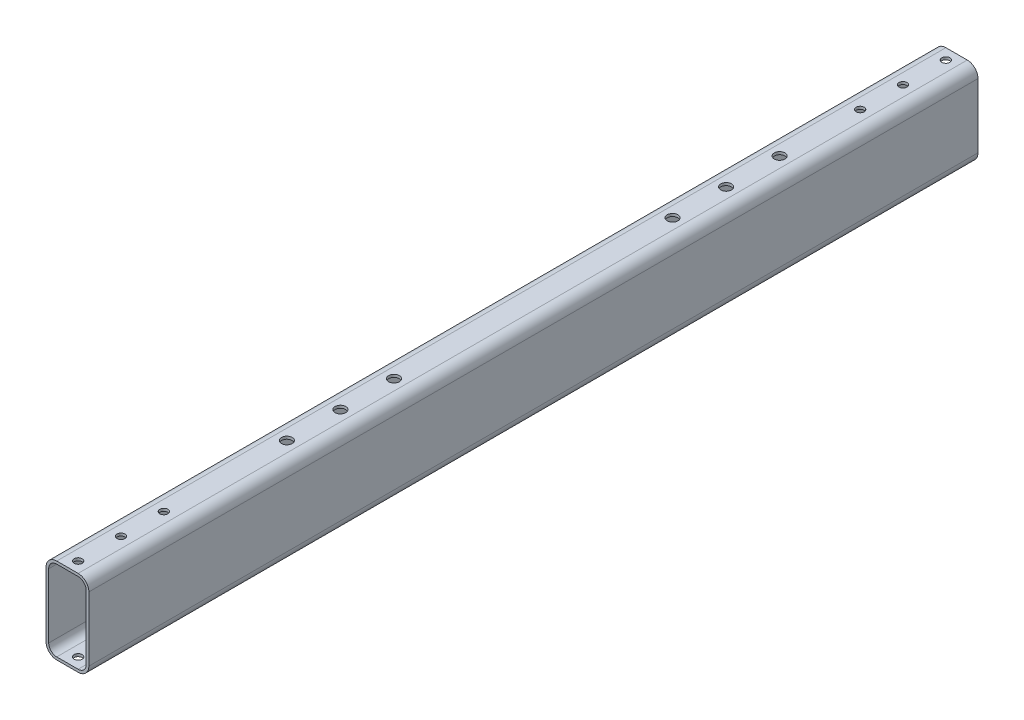
SolidWorks part; units mm, degrees
material "6061-T6 (SS)"
ref_plane "Front Plane" through (0, 0, 0) normal (0, 0, 1) x (1, 0, 0)
ref_plane "Top Plane" through (0, 0, 0) normal (0, 1, 0) x (1, 0, 0)
ref_plane "Right Plane" through (0, 0, 0) normal (1, 0, 0) x (0, 0, -1)
sketch "Sketch1" plane through (0, 0, 0) normal (0, 0, 1) x (1, 0, 0)
  line L1 (-6.35, -25.4) -> (6.35, -25.4)
  line L2 (-12.7, -19.05) -> (-12.7, 19.05)
  line L3 (-6.35, 25.4) -> (6.35, 25.4)
  line L4 (12.7, -19.05) -> (12.7, 19.05)
  line L5 (-12.7, -25.4) -> (12.7, 25.4) construction
  line L6 (-12.7, 25.4) -> (12.7, -25.4) construction
  arc A0 (-12.7, -19.05) -> (-6.35, -25.4) centre (-6.35, -19.05) ccw
  arc A1 (6.35, -25.4) -> (12.7, -19.05) centre (6.35, -19.05) ccw
  arc A2 (6.35, 25.4) -> (12.7, 19.05) centre (6.35, 19.05) cw
  arc A3 (-12.7, 19.05) -> (-6.35, 25.4) centre (-6.35, 19.05) cw
  point P0 (0, 0)
  dimension "D3" = 6.35
  dimension "D1" = 50.8
  dimension "D2" = 25.4
extrude "Extrude-Thin1" add sketch "Sketch1" along normal blind 527.05 thin thin type one direction reverse wall 1.5875
hole_wizard "3/16 (0.1875) Diameter Hole1" positions "3DSketch1" profile "Sketch3" hole size "3/16" standard "ANSI Inch" end condition through all
sketch3d "3DSketch1"
  line L1 (6.35, 25.4, 0) -> (-6.35, 25.4, 0) construction
  line L6 (0, 25.4, 527.05) -> (0, 25.4, 0) construction
  line L7 (6.35, 25.4, 527.05) -> (-6.35, 25.4, 527.05) construction
  point P57 (0, 25.4, 6.35)
  point P59 (0, 25.4, 31.75)
  point P61 (0, 25.4, 57.15)
  point P63 (0, 25.4, 495.3)
  point P65 (0, 25.4, 469.9)
  point P67 (0, 25.4, 520.7)
  dimension "D1" = 25.4
  dimension "D2" = 25.4
  dimension "D3" = 6.35
  dimension "D4" = 25.4
  dimension "D5" = 25.4
  dimension "D6" = 6.35
sketch "Sketch3" plane through (0, 25.4, 520.7) normal (1, 0, 0) x (0, 0, 1)
  line L0 (0, 0) -> (0, 50.8)
  line L1 (0, 50.8) -> (2.3812, 50.8)
  line L2 (2.3812, 50.8) -> (2.3812, 0)
  line L5 (2.3812, 0) -> (0, 0)
  line L11 (0, -6.35) -> (0, 107.95) construction
  dimension "Thru Hole Dia." = 4.7625
  dimension "Thru Hole Depth" = 50.8
hole_wizard "3/16 (0.195) Diameter Hole1" positions "Sketch4" profile "Sketch5" hole size "3/16" standard "ANSI Inch" end condition up to next
sketch "Sketch4" plane through (0, -25.4, 0) normal (0, -1, 0) x (-1, 0, 0)
  point P3 (3.175, -89.4447)
  point P6 (-3.175, -114.8447)
  point P9 (3.175, -140.2447)
  point P12 (-3.175, -165.6447)
  point P15 (-3.175, -318.0447)
  point P18 (3.175, -343.4447)
  point P21 (-3.175, -368.8447)
  point P24 (3.175, -394.2447)
sketch "Sketch5" plane through (-3.175, -25.4, 89.4447) normal (1, 0, 0) x (0, 0, -1)
  line L0 (0, 0) -> (0, 1.5875)
  line L1 (0, 1.5875) -> (2.4765, 1.5875)
  line L2 (2.4765, 1.5875) -> (2.4765, 0)
  line L5 (2.4765, 0) -> (0, 0)
  line L11 (0, -6.35) -> (0, 107.95) construction
  dimension "Thru Hole Dia." = 4.953
  dimension "Thru Hole Depth" = 1.5875
hole_wizard "1/4 (0.25) Diameter Hole1" positions "Sketch7" profile "Sketch6" hole size "1/4" standard "ANSI Inch"
sketch "Sketch7" plane through (0, 25.4, 0) normal (0, 1, 0) x (1, 0, 0)
  point P0 (0, -104.85)
  point P3 (0, -136.6)
  point P6 (0, -168.35)
  point P9 (0, -396.9748)
  point P12 (0, -365.2248)
  point P15 (0, -333.4748)
sketch "Sketch6" plane through (0, 25.4, 104.85) normal (1, 0, 0) x (0, 0, 1)
  line L0 (0, 0) -> (0, 27.3077)
  line L1 (0, 27.3077) -> (3.175, 25.4)
  line L2 (3.175, 25.4) -> (3.175, 0)
  line L5 (3.175, 0) -> (0, 0)
  line L10 (0, 27.3077) -> (-3.175, 25.4) construction
  line L11 (0, -6.35) -> (0, 107.95) construction
  dimension "Hole Dia." = 6.35
  dimension "Hole Depth" = 25.4
  dimension "Drill Angle" = 118
